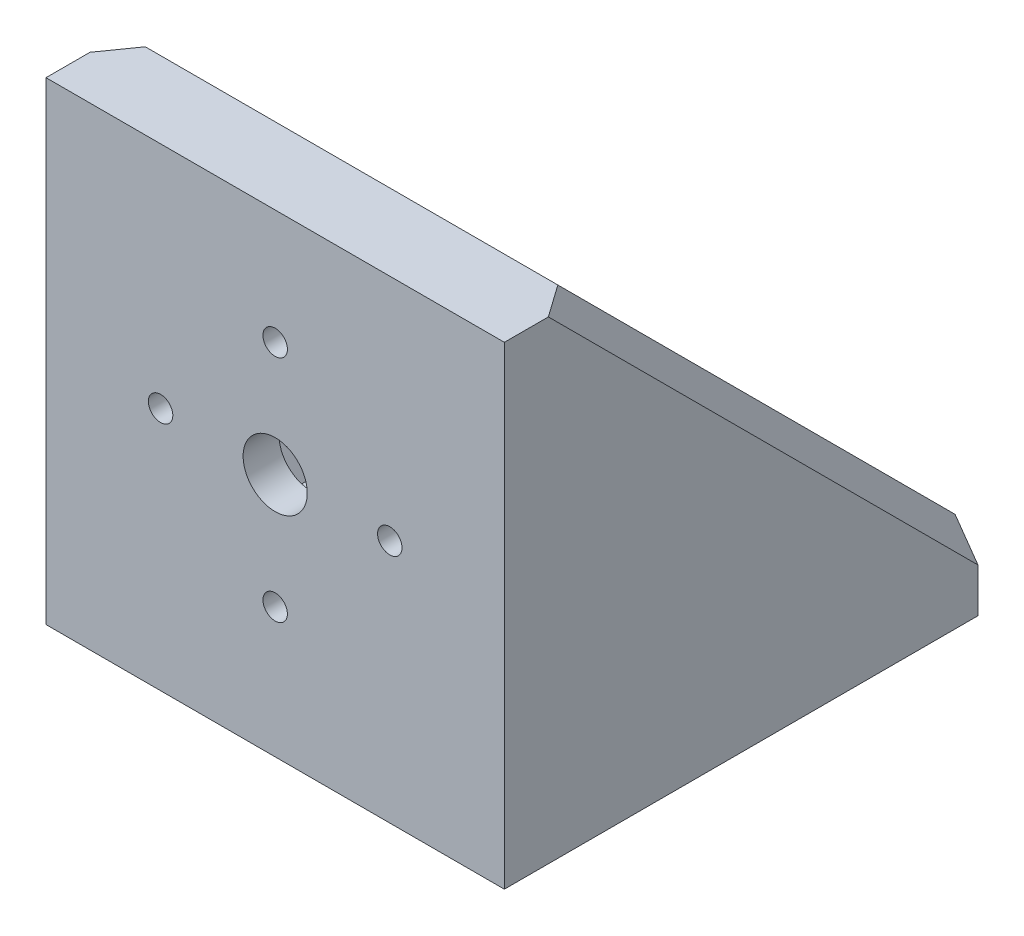
SolidWorks part; units mm, degrees
ref_plane "Front Plane" through (0, 0, 0) normal (0, 0, 1) x (1, 0, 0)
ref_plane "Top Plane" through (0, 0, 0) normal (0, 1, 0) x (1, 0, 0)
ref_plane "Right Plane" through (0, 0, 0) normal (1, 0, 0) x (0, 0, -1)
sketch "Sketch1" plane through (0, 0, 0) normal (1, 0, 0) x (0, 0, -1)
  line L0 (0, 62) -> (0, 0)
  line L1 (0, 0) -> (62, 0)
  line L2 (62, 0) -> (62, 10)
  line L3 (62, 10) -> (10, 10)
  line L4 (10, 10) -> (10, 62)
  line L5 (10, 62) -> (0, 62)
  dimension "D1" = 62
  dimension "D2" = 62
  dimension "D3" = 10
  dimension "D4" = 10
extrude "Body" add sketch "Sketch1" along normal blind 60
ref_plane "Midplane" through (30, 0, 0) normal (1, 0, 0) x (0, 0, -1)
sketch "Sketch2" plane through (0, 0, 0) normal (1, 0, 0) x (0, 0, -1)
  line L0 (62, 10) -> (10, 10) construction
  line L1 (10, 10) -> (10, 62) construction
  line L2 (62, 10) -> (10, 10)
  line L3 (10, 10) -> (10, 62)
  line L4 (10, 62) -> (62, 10)
extrude "Support Arm" add sketch "Sketch2" along normal blind 10
mirror "Support Arm Mirror" about plane through (30, 0, 0) normal (1, 0, 0) of "Support Arm"
ref_plane "45 Degree Symmetry Plane" through (0, 0, 0) normal (0, 0.7071, 0.7071) x (-1, 0, 0)
ref_plane "Inner Front Face Plane" through (0, 0, -10) normal (0, 0, -1) x (-1, 0, 0)
sketch "Sketch3" plane through (0, 0, -10) normal (0, 0, -1) x (-1, 0, 0)
  line L0 (0, 62) -> (-60, 2) construction
  line L1 (-30, 32) -> (-30, 47) construction
  line L2 (-60, 0) -> (0, 0) construction
  line L5 (-60, 0) -> (0, 0) construction
  line L7 (-60, 62) -> (-60, 0) construction
  circle A0 centre (-30, 32) radius 4.2
  circle A1 centre (-30, 32) radius 15 construction
  circle A2 centre (-30, 47) radius 1.6
  circle A3 centre (-15, 32) radius 1.6
  circle A4 centre (-30, 17) radius 1.6
  circle A5 centre (-45, 32) radius 1.6
  point P18 (-30, 32)
  dimension "D1" = 8.4
  dimension "D2" = 3.2
  dimension "D4" = 30
  dimension "D5" = 2
  dimension "D3" = 4
extrude "Holes" cut sketch "Sketch3" against normal up to next
sketch "Sketch5" plane through (0, 0, -10) normal (0, 0, -1) x (-1, 0, 0)
  line L1 (-26.1895, 38.6) -> (-33.8105, 38.6)
  line L2 (-33.8105, 38.6) -> (-37.621, 32)
  line L3 (-37.621, 32) -> (-33.8105, 25.4)
  line L4 (-33.8105, 25.4) -> (-26.1895, 25.4)
  line L5 (-26.1895, 25.4) -> (-22.379, 32)
  line L6 (-22.379, 32) -> (-26.1895, 38.6)
  circle A0 centre (-30, 32) radius 6.6 construction
  dimension "D1" = 13.2
extrude "Shaft Hole Counterbore" cut sketch "Sketch5" against normal blind 5.3
sketch "Sketch6" plane through (0, 0, -10) normal (0, 0, -1) x (-1, 0, 0)
  line L0 (-12.15, 30.3546) -> (-12.15, 33.6454)
  line L1 (-28.3546, 49.85) -> (-31.6454, 49.85)
  line L2 (-31.6454, 49.85) -> (-33.2909, 47)
  line L3 (-33.2909, 47) -> (-31.6454, 44.15)
  line L4 (-31.6454, 44.15) -> (-28.3546, 44.15)
  line L5 (-28.3546, 44.15) -> (-26.7091, 47)
  line L6 (-26.7091, 47) -> (-28.3546, 49.85)
  line L7 (-12.15, 33.6454) -> (-15, 35.2909)
  line L8 (-15, 35.2909) -> (-17.85, 33.6454)
  line L9 (-17.85, 33.6454) -> (-17.85, 30.3546)
  line L10 (-17.85, 30.3546) -> (-15, 28.7091)
  line L11 (-15, 28.7091) -> (-12.15, 30.3546)
  line L12 (-31.6454, 14.15) -> (-28.3546, 14.15)
  line L13 (-28.3546, 14.15) -> (-26.7091, 17)
  line L14 (-26.7091, 17) -> (-28.3546, 19.85)
  line L15 (-28.3546, 19.85) -> (-31.6454, 19.85)
  line L16 (-31.6454, 19.85) -> (-33.2909, 17)
  line L17 (-33.2909, 17) -> (-31.6454, 14.15)
  line L18 (-47.85, 33.6454) -> (-47.85, 30.3546)
  line L19 (-47.85, 30.3546) -> (-45, 28.7091)
  line L20 (-45, 28.7091) -> (-42.15, 30.3546)
  line L21 (-42.15, 30.3546) -> (-42.15, 33.6454)
  line L22 (-42.15, 33.6454) -> (-45, 35.2909)
  line L23 (-45, 35.2909) -> (-47.85, 33.6454)
  circle A0 centre (-30, 47) radius 2.85 construction
  point P33 (-30, 32)
  dimension "D2" = 4
  dimension "D1" = 5.7
extrude "Mounting Holes Counterbore" cut sketch "Sketch6" against normal blind 3.5
mirror "Mounting Feature Mirror" about plane through (0, 0, 0) normal (0, 0.7071, 0.7071) of "Shaft Hole Counterbore", "Holes", "Mounting Holes Counterbore"
chamfer "Chamfer1" distance 3 angle 45 7 edges at (0, 36, -36) (60, 36, -36) (50, 10, -36) (50, 36, -10) (10, 10, -36) (10, 36, -10) (30, 10, -10)
equation "\"Width\"= 60mm"
equation "\"Height\"= 62mm"
equation "\"Depth\"= 62mm"
equation "\"Thick\"= 10mm"
equation "\"D2@Sketch1\"=\"Height\""
equation "\"D1@Sketch1\"=\"Depth\""
equation "\"D3@Sketch1\"=\"Thick\""
equation "\"D4@Sketch1\"=\"Thick\""
equation "\"D1@Support Arm\"=\"Thick\""
equation "\"D1@Midplane\"=\"Width\"/2"
equation "\"D1@Inner Front Face Plane\" = \"Thick\""
